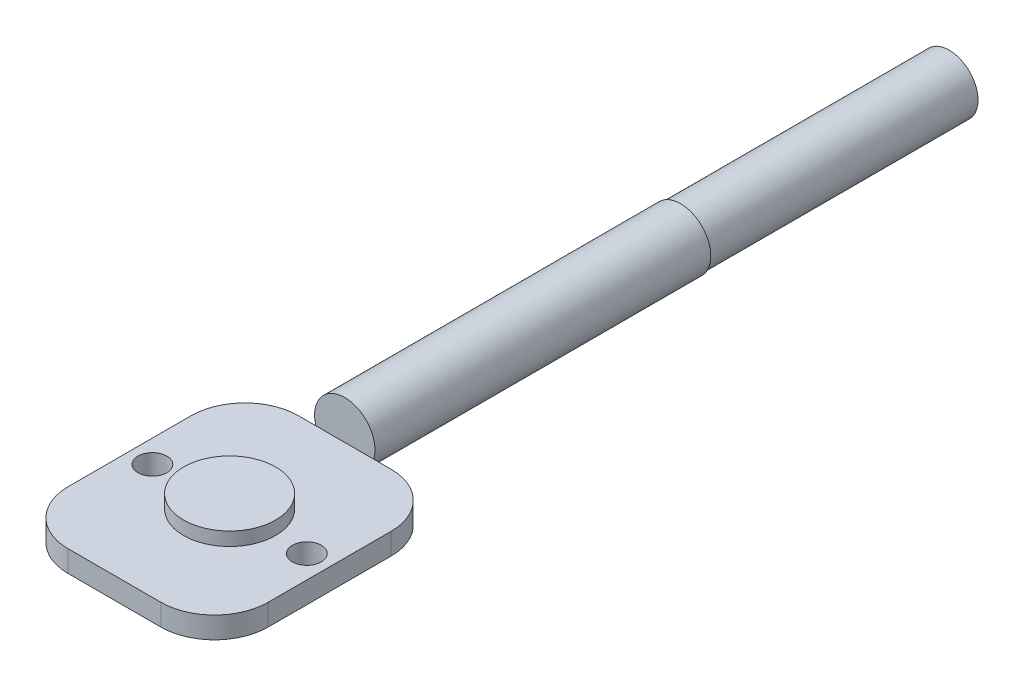
SolidWorks part; units mm, degrees
ref_plane "Front Plane" through (0, 0, 0) normal (0, 0, 1) x (1, 0, 0)
ref_plane "Top Plane" through (0, 0, 0) normal (0, 1, 0) x (1, 0, 0)
ref_plane "Right Plane" through (0, 0, 0) normal (1, 0, 0) x (0, 0, -1)
sketch "Sketch1" plane through (0, 0, 0) normal (0, 1, 0) x (1, 0, 0)
  line L0 (-3.45, 8.575) -> (3.45, 8.575)
  line L1 (7.45, 4.575) -> (7.45, -4.575)
  line L2 (3.45, -8.575) -> (-3.45, -8.575)
  line L3 (-7.45, -4.575) -> (-7.45, 4.575)
  line L4 (-7.45, 8.575) -> (7.45, -8.575) construction
  line L5 (-5.75, 0) -> (5.75, 0) construction
  arc A0 (-3.45, -8.575) -> (-7.45, -4.575) centre (-3.45, -4.575) cw
  arc A1 (7.45, -4.575) -> (3.45, -8.575) centre (3.45, -4.575) cw
  arc A2 (7.45, 4.575) -> (3.45, 8.575) centre (3.45, 4.575) ccw
  arc A3 (-3.45, 8.575) -> (-7.45, 4.575) centre (-3.45, 4.575) ccw
  circle A4 centre (-5.75, 0) radius 1.075
  circle A5 centre (5.75, 0) radius 1.075
  point P12 (7.45, 8.575)
  dimension "D3" = 4
  dimension "D4" = 2.15
  dimension "D1" = 14.9
  dimension "D2" = 17.15
  dimension "D5" = 11.5
extrude "Boss-Extrude1" add sketch "Sketch1" along normal blind 1.6
sketch "Sketch2" plane through (0, 1.6, 0) normal (0, 1, 0) x (1, 0, 0)
  circle A0 centre (0, 0) radius 3.4265
extrude "Boss-Extrude2" add sketch "Sketch2" along normal blind 1
sketch "Sketch4" plane through (0, 0, -8.575) normal (0, 0, -1) x (-1, 0, 0)
  line L3 (0, 0) -> (0, 2.25) construction
  circle A2 centre (0, 2.25) radius 2.25
  dimension "D1" = 4.5
extrude "Boss-Extrude3" add sketch "Sketch4" along normal blind 25 separate body
ref_axis "Axis1" through (0, 4.725, 0) along (0, -1, 0)
sketch "Sketch5" plane through (0, 0, -33.575) normal (0, 0, -1) x (-1, 0, 0)
  circle A0 centre (0, 2.25) radius 2.25 construction
  circle A1 centre (0, 2.25) radius 2.25 construction
  circle A2 centre (0, 2.25) radius 2.15
  dimension "D1" = 0.1
extrude "Boss-Extrude4" add sketch "Sketch5" along normal blind 20
